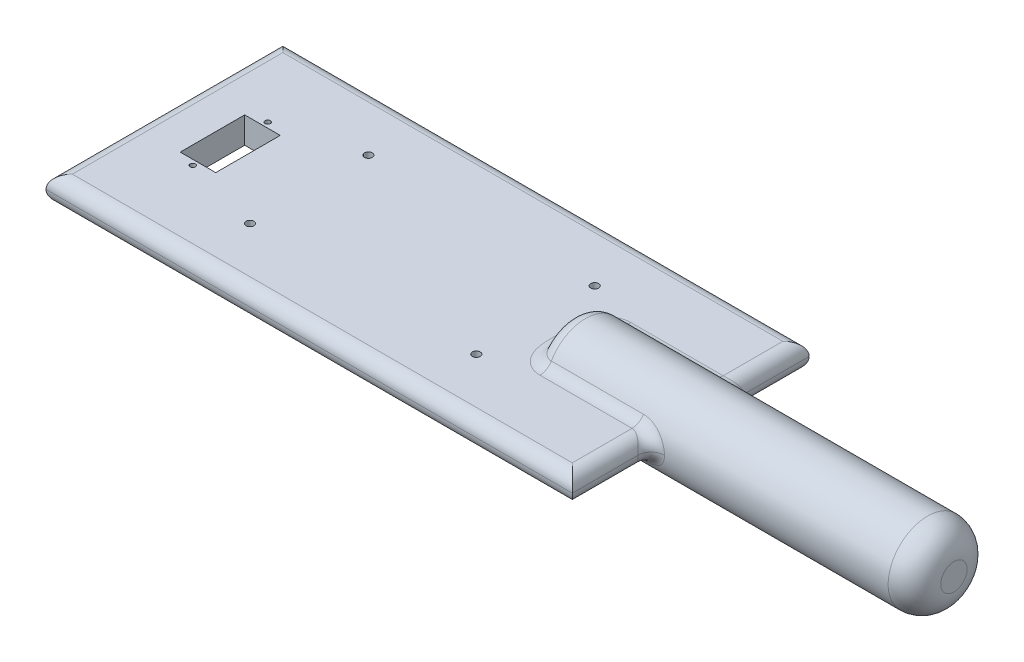
SolidWorks part; units mm, degrees
ref_plane "Alzado" through (0, 0, 0) normal (0, 0, 1) x (1, 0, 0)
ref_plane "Planta" through (0, 0, 0) normal (0, 1, 0) x (1, 0, 0)
ref_plane "Vista lateral" through (0, 0, 0) normal (1, 0, 0) x (0, 0, -1)
sketch "Croquis1" plane through (0, 0, 0) normal (0, 1, 0) x (1, 0, 0)
  line L0 (0, 0) -> (49310.8582, 0) construction
  line L1 (0, 0) -> (0, 49310.8582) construction
  line L3 (-100, -45) -> (100, -45)
  line L4 (-100, -45) -> (-100, 45)
  line L5 (-100, 45) -> (100, 45)
  line L6 (100, -45) -> (100, 45)
  line L7 (-100, -45) -> (100, 45) construction
  line L8 (-100, 45) -> (100, -45) construction
  line L9 (-81.75, -12.25) -> (-68.25, -12.25)
  line L10 (-81.75, -12.25) -> (-81.75, 12.25)
  line L11 (-81.75, 12.25) -> (-68.25, 12.25)
  line L12 (-68.25, -12.25) -> (-68.25, 12.25)
  line L13 (-81.75, -12.25) -> (-68.25, 12.25) construction
  line L14 (-81.75, 12.25) -> (-68.25, -12.25) construction
  circle A0 centre (-75, 14.25) radius 1
  circle A2 centre (-75, -14.25) radius 1
  point P5 (0, 0)
  point P10 (-75, 0)
  dimension "D5" = 2
  dimension "D1" = 90
  dimension "D2" = 200
  dimension "D3" = 24.5
  dimension "D4" = 13.5
  dimension "D6" = 2
  dimension "D7" = 75
extrude "Base" add sketch "Croquis1" along normal blind 10
sketch "Croquis2" plane through (0, 10, 0) normal (0, 1, 0) x (1, 0, 0)
  line L0 (0, 0) -> (50000, 0) construction
  line L1 (100, -45) -> (100, 45) construction
  line L2 (100, 45) -> (-100, 45) construction
  circle A0 centre (-45, 22.5) radius 1.5
  circle A3 centre (41, 22.5) radius 1.5
  circle A4 centre (41, -22.5) radius 1.5
  circle A5 centre (-45, -22.5) radius 1.5
  dimension "D1" = 3
  dimension "D2" = 45
  dimension "D4" = 3
  dimension "D5" = 22.5
  dimension "D6" = 86
extrude "Cortar-Extruir1" cut sketch "Croquis2" against normal through all
sketch "Croquis3" plane through (100, 0, 0) normal (1, 0, 0) x (0, 0, -1)
  line L0 (-45, 10) -> (-45, 0) construction
  circle A0 centre (0, 5) radius 15
  point P6 (-45, 5)
  dimension "D1" = 30
extrude "Mango" add sketch "Croquis3" along normal blind 100 and the other way blind 45
fillet "Redondeo Mango" radius 10 1 edges at (200, 5, -15)
fillet "Redondeo1" radius 5 5 edges at (0, 0, 45) (-100, 0, 0) (0, 0, -45) (100, 0, -29.5711) (100, 0, 29.5711)
fillet "Redondeo2" radius 5 11 edges at (-100, 10, 0) (0, 10, 45) (100, 10, 29.5711) (100, 10, -29.5711) (100, 7.5365, -14.784) (0, 10, -45) (100, 7.5, 45) (-100, 7.5, 45) (-100, 7.5, -45) (100, 7.5, -45) (100, 7.5365, 14.784)
fillet "Redondeo3" radius 5 12 edges at (98.9788, 8.0281, -14.6912) (55, 0, 0) (55, 10, 0) (55, 20, 0) (55, -10, 0) (75, 0, -14.1421) (75, 10, -14.1421) (75, 0, 14.1421) (98.9788, 1.9719, -14.6912) (98.9788, 1.9719, 14.6912) (75, 10, 14.1421) (98.9788, 8.0281, 14.6912)
